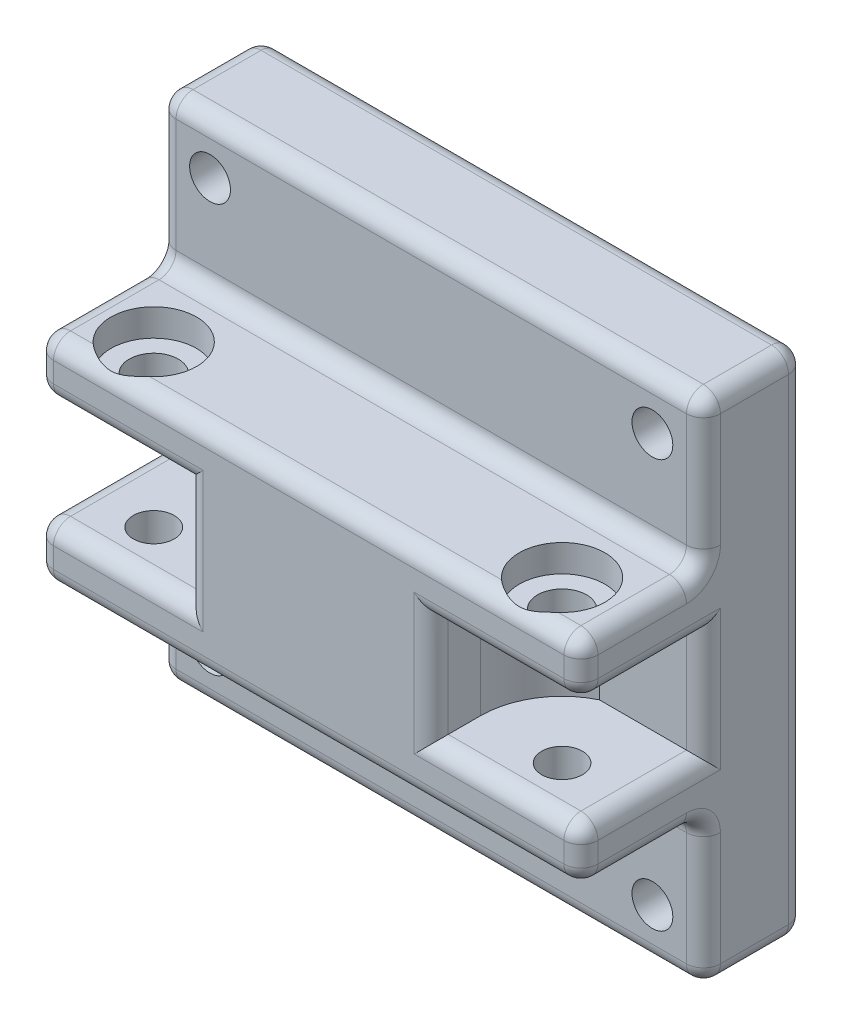
SolidWorks part; units mm, degrees
ref_plane "Front Plane" through (0, 0, 0) normal (0, 0, 1) x (1, 0, 0)
ref_plane "Top Plane" through (0, 0, 0) normal (0, 1, 0) x (1, 0, 0)
ref_plane "Right Plane" through (0, 0, 0) normal (1, 0, 0) x (0, 0, -1)
sketch "Sketch1" plane through (0, 0, 0) normal (0, 0, 1) x (1, 0, 0)
  line L1 (0, 0) -> (50.8, 0)
  line L2 (0, 0) -> (0, 47.625)
  line L3 (0, 47.625) -> (50.8, 47.625)
  line L4 (50.8, 0) -> (50.8, 47.625)
  dimension "D1" = 50.8
  dimension "D2" = 47.625
extrude "Boss-Extrude1" add sketch "Sketch1" along normal blind 9.525
ref_plane "Plane1" through (25.4, 0, 0) normal (1, 0, 0) x (0, 0, -1)
ref_plane "Plane2" through (0, 23.8125, 0) normal (0, -1, 0) x (-1, 0, 0)
sketch "Sketch2" plane through (0, 0, 9.525) normal (0, 0, 1) x (1, 0, 0)
  line L0 (0, 47.625) -> (0, 0) construction
  line L1 (50.8, 47.625) -> (0, 47.625) construction
  line L2 (0, 0) -> (50.8, 0) construction
  circle A0 centre (4.7625, 42.8625) radius 1.905
  circle A1 centre (4.7625, 4.7625) radius 1.905
  dimension "D2" = 4.7625
  dimension "D3" = 3.81
  dimension "D6" = 3.81
  dimension "D1" = 4.7625
  dimension "D4" = 4.7625
  dimension "D5" = 4.7625
extrude "Cut-Extrude1" cut sketch "Sketch2" against normal through all
sketch "Sketch3" plane through (0, 0, 9.525) normal (0, 0, 1) x (1, 0, 0)
  line L0 (0, 47.625) -> (0, 0) construction
  line L1 (0, 33.8455) -> (50.8, 33.8455)
  line L2 (0, 33.8455) -> (0, 28.7655)
  line L3 (0, 28.7655) -> (50.8, 28.7655)
  line L4 (50.8, 33.8455) -> (50.8, 28.7655)
  line L5 (25.4, 13.7795) -> (25.4, 0) construction
  line L6 (50.8, 0) -> (50.8, 47.625) construction
  line L7 (25.4, 33.8455) -> (25.4, 47.625) construction
  line L8 (0, 13.7795) -> (50.8, 13.7795)
  line L9 (0, 13.7795) -> (0, 18.8595)
  line L10 (0, 18.8595) -> (50.8, 18.8595)
  line L11 (50.8, 13.7795) -> (50.8, 18.8595)
  line L12 (0, 0) -> (50.8, 0) construction
  line L13 (50.8, 47.625) -> (0, 47.625) construction
  dimension "D2" = 5.08
  dimension "D3" = 9.906
  dimension "D4" = 5.08
extrude "Boss-Extrude2" add sketch "Sketch3" along normal blind 11.43
sketch "Sketch4" plane through (0, 33.8455, 0) normal (0, 1, 0) x (1, 0, 0)
  line L2 (50.8, 0) -> (0, 0) construction
  line L3 (0, -9.525) -> (0, 0) construction
  circle A1 centre (6.35, -16.3639) radius 2.286
  dimension "D1" = 16.3639
  dimension "D3" = 4.572
  dimension "D2" = 6.35
extrude "Cut-Extrude2" cut sketch "Sketch4" against normal up to surface (5.08 mm away) and the other way through all up to face at (25.4, 28.7655, 15.24)
ref_plane "Plane3" through (25.4, 0, 0) normal (1, 0, 0) x (0, 0, -1)
mirror "Mirror3" about plane through (25.4, 0, 0) normal (1, 0, 0) of "Cut-Extrude1", "Cut-Extrude2"
sketch "Sketch5" plane through (0, 33.8455, 0) normal (0, 1, 0) x (1, 0, 0)
  circle A0 centre (6.35, -16.3639) radius 4.0005
  circle A1 centre (44.45, -16.3639) radius 4.0005
  dimension "D1" = 8.001
extrude "Cut-Extrude3" cut sketch "Sketch5" against normal blind 2.54
sketch "Sketch8" plane through (0, 18.8595, 0) normal (0, 1, 0) x (1, 0, 0)
  line L0 (36.83, -16.3639) -> (36.83, -20.955)
  line L1 (50.8, -20.955) -> (0, -20.955) construction
  line L2 (13.97, -16.3639) -> (13.97, -20.955)
  line L3 (13.97, -20.955) -> (36.83, -20.955)
  line L4 (9.7105, -9.525) -> (41.0895, -9.525)
  line L5 (50.8, -9.525) -> (0, -9.525) construction
  arc A0 (41.0895, -9.525) -> (36.83, -16.3639) centre (44.45, -16.3639) ccw
  arc A1 (13.97, -16.3639) -> (9.7105, -9.525) centre (6.35, -16.3639) ccw
  point P16 (9.7105, -9.525)
  dimension "D1" = 15.24
  dimension "D2" = 15.24
extrude "Boss-Extrude3" add sketch "Sketch8" along normal up to surface (9.906 mm away) up to face at (44.45, 28.7655, 18.6499)
sketch "Sketch9" plane through (0, 18.8595, 0) normal (0, 1, 0) x (1, 0, 0)
  circle A0 centre (44.45, -16.3639) radius 1.905
  circle A1 centre (6.35, -16.3639) radius 1.905
  circle A2 centre (6.35, -16.3639) radius 2.286 construction
  point P7 (6.35, -16.3639)
  dimension "D1" = 3.81
  dimension "D2" = 3.81
extrude "Cut-Extrude4" cut sketch "Sketch9" against normal up to surface (5.08 mm away) up to face at (25.4, 13.7795, 15.24)
sketch "Sketch11" plane through (0, 0, 0) normal (0, 0, -1) x (-1, 0, 0)
  line L0 (-25.4, 47.625) -> (-25.4, 0) construction
  line L1 (-50.8, 47.625) -> (0, 47.625) construction
  line L2 (0, 0) -> (-50.8, 0) construction
  line L3 (-50.8, 23.8125) -> (0, 23.8125) construction
  line L4 (-50.8, 0) -> (-50.8, 47.625) construction
  line L5 (0, 47.625) -> (0, 0) construction
  circle A0 centre (-44.45, 30.1625) radius 1.905
  circle A1 centre (-44.45, 17.4625) radius 1.905
  circle A2 centre (-6.35, 17.4625) radius 1.905
  circle A3 centre (-6.35, 30.1625) radius 1.905
  point P16 (0, 0)
  point P17 (0, 0)
  point P18 (0, 0)
  dimension "D2" = 3.81
  dimension "D1" = 12.7
  dimension "D3" = 6.35
  dimension "D4" = 19.05
extrude "Cut-Extrude5" cut sketch "Sketch11" against normal blind 6.35
fillet "Fillet1" radius 1.5875 38 edges at (25.4, 47.625, 9.525) (25.4, 47.625, 0) (25.4, 0, 9.525) (25.4, 0, 0) (50.8, 0, 4.7625) (50.8, 6.8898, 9.525) (50.8, 13.7795, 15.24) (50.8, 18.8595, 15.24) (50.8, 23.8125, 9.525) (50.8, 28.7655, 15.24) (50.8, 33.8455, 15.24) (50.8, 40.7353, 9.525) (50.8, 47.625, 4.7625) (50.8, 23.8125, 0) (25.4, 33.8455, 20.955) (50.8, 31.3055, 20.955) (43.815, 28.7655, 20.955) (36.83, 23.8125, 20.955) (43.815, 18.8595, 20.955) (50.8, 16.3195, 20.955) (25.4, 13.7795, 20.955) (6.985, 18.8595, 20.955) (13.97, 23.8125, 20.955) (6.985, 28.7655, 20.955) (0, 47.625, 4.7625) (0, 40.7353, 9.525) (0, 33.8455, 15.24) (0, 31.3055, 20.955) (0, 28.7655, 15.24) (0, 23.8125, 9.525) (0, 18.8595, 15.24) (0, 16.3195, 20.955) (0, 13.7795, 15.24) (0, 6.8898, 9.525) (0, 0, 4.7625) (0, 23.8125, 0) (25.4, 33.8455, 9.525) (25.4, 13.7795, 9.525)
